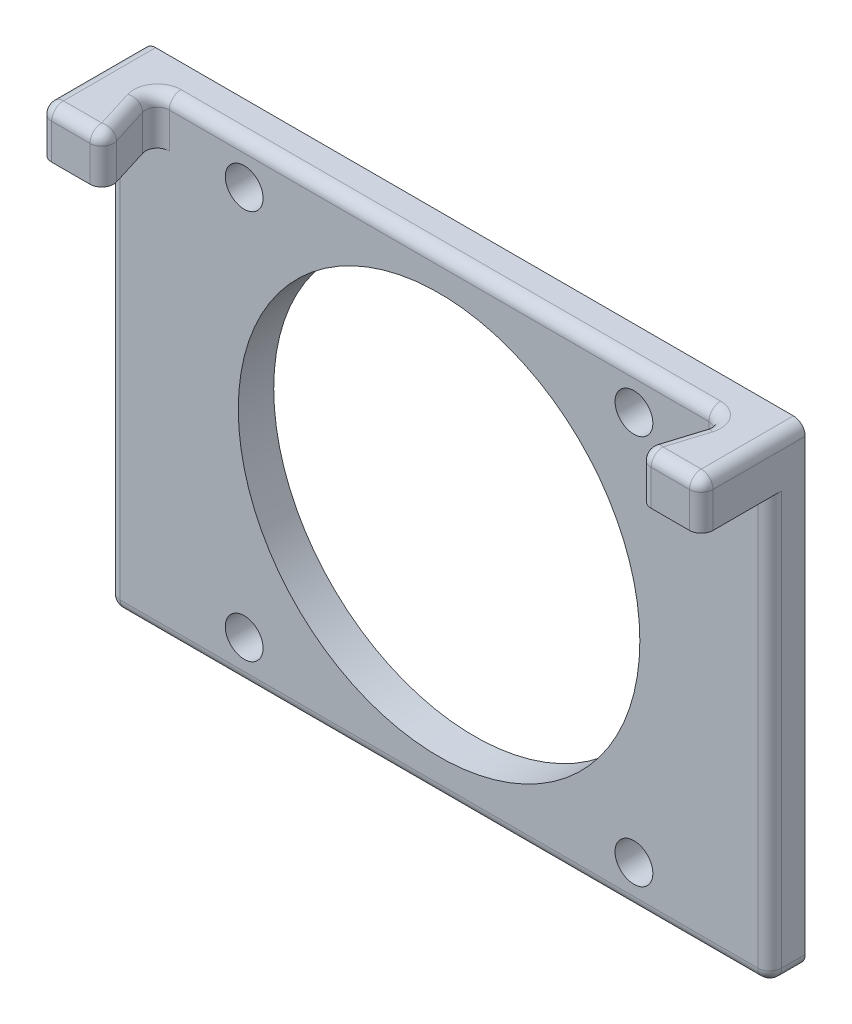
SolidWorks part; units mm, degrees
ref_plane "Plan de face" through (0, 0, 0) normal (0, 0, 1) x (1, 0, 0)
ref_plane "Plan de dessus" through (0, 0, 0) normal (0, 1, 0) x (1, 0, 0)
ref_plane "Plan de droite" through (0, 0, 0) normal (1, 0, 0) x (0, 0, -1)
sketch "Esquisse1" plane through (0, 0, 0) normal (0, 0, 1) x (1, 0, 0)
  line L1 (-28, 20) -> (28, 20)
  line L2 (-28, 20) -> (-28, -20)
  line L3 (-28, -20) -> (28, -20)
  line L4 (28, 20) -> (28, -20)
  dimension "D1" = 56
  dimension "D2" = 40
  dimension "D3" = 28
  dimension "D4" = 20
extrude "Boss.-Extru.1" add sketch "Esquisse1" along normal blind 3
sketch "Esquisse2" plane through (0, 0, 3) normal (0, 0, 1) x (1, 0, 0)
  line L1 (-28, 20) -> (-24.2, 20)
  line L2 (-28, 20) -> (-28, 16)
  line L3 (-28, 16) -> (-24.2, 16)
  line L4 (-24.2, 20) -> (-24.2, 16)
  line L5 (28, 20) -> (24.2, 20)
  line L6 (28, 20) -> (28, 16)
  line L7 (28, 16) -> (24.2, 16)
  line L8 (24.2, 20) -> (24.2, 16)
  dimension "D1" = 4
  dimension "D2" = 4
  dimension "D3" = 3.8
  dimension "D4" = 3.8
extrude "Boss.-Extru.2" add sketch "Esquisse2" along normal blind 5.8
sketch "Esquisse3" plane through (0, 20, 0) normal (0, 1, 0) x (1, 0, 0)
  line L0 (-24.2, -3) -> (-22.4, -8.8)
  line L1 (-22.4, -8.8) -> (-24.2, -8.8)
  line L2 (-24.2, -8.8) -> (-24.2, -3)
  line L3 (24.2, -3) -> (24.2, -8.8)
  line L4 (24.2, -8.8) -> (22.4, -8.8)
  line L5 (22.4, -8.8) -> (24.2, -3)
  dimension "D1" = 1.8
  dimension "D2" = 1.8
extrude "Boss.-Extru.3" add sketch "Esquisse3" against normal up to surface (4 mm away) up to face at (-26.575, 16, 6.625)
fillet "Congé1" radius 1 18 edges at (23.3, 20, 5.9) (28, -20, 1.5) (-28, -20, 1.5) (-28, 20, 4.4) (28, 20, 4.4) (25.2, 20, 8.8) (-25.2, 20, 8.8) (0, -20, 3) (28, -2, 3) (24.2, 18, 3) (22.4, 18, 8.8) (28, 18, 8.8) (-28, 18, 8.8) (-22.4, 18, 8.8)
sketch "Esquisse4" plane through (0, 0, 0) normal (0, 0, -1) x (-1, 0, 0)
  line L0 (-27, 20) -> (27, 20) construction
  line L1 (-20, 20) -> (20, 20)
  line L2 (-20, 20) -> (-20, -20)
  line L3 (-20, -20) -> (20, -20)
  line L4 (20, 20) -> (20, -20)
  line L5 (27, -20) -> (-27, -20) construction
  circle A0 centre (-16.5, 16.5) radius 1.6
  circle A1 centre (16.5, 16.5) radius 1.6
  circle A2 centre (16.5, -16.5) radius 1.6
  circle A3 centre (-16.5, -16.5) radius 1.6
  dimension "D3" = 3.2
  dimension "D4" = 3.2
  dimension "D5" = 3.2
  dimension "D6" = 3.2
  dimension "D1" = 40
  dimension "D2" = 20
  dimension "D7" = 3.5
  dimension "D8" = 3.5
  dimension "D9" = 3.5
  dimension "D10" = 3.5
  dimension "D11" = 3.5
  dimension "D12" = 3.5
  dimension "D13" = 3.5
  dimension "D14" = 3.5
extrude "Enlèv. mat.-Extru.1" cut sketch "Esquisse4" against normal through all contours A0 | A3 | A1 | A2 region at (16.5, 16.5, 0) region at (-16.5, 16.5, 0) region at (16.5, -16.5, 0)
sketch "Esquisse5" plane through (0, 0, 0) normal (0, 0, -1) x (-1, 0, 0)
  circle A0 centre (0, 0) radius 17
  dimension "D1" = 34
extrude "Enlèv. mat.-Extru.2" cut sketch "Esquisse5" against normal through all
